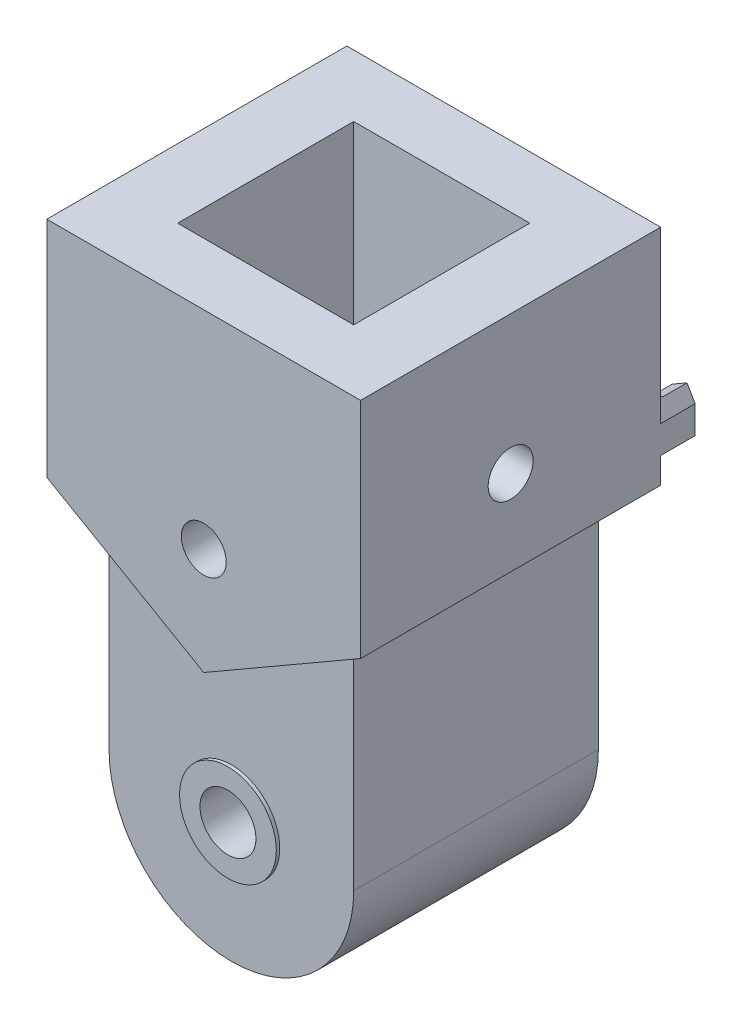
SolidWorks part; units mm, degrees
material "PETG"
ref_plane "Front Plane" through (0, 0, 0) normal (0, 0, 1) x (1, 0, 0)
ref_plane "Top Plane" through (0, 0, 0) normal (0, 1, 0) x (1, 0, 0)
ref_plane "Right Plane" through (0, 0, 0) normal (1, 0, 0) x (0, 0, -1)
sketch "Sketch1" plane through (0, 0, 0) normal (0, 1, 0) x (1, 0, 0)
  line L1 (-12.7375, -12.7375) -> (12.7375, -12.7375)
  line L2 (-12.7375, -12.7375) -> (-12.7375, 12.7375)
  line L3 (-12.7375, 12.7375) -> (12.7375, 12.7375)
  line L4 (12.7375, -12.7375) -> (12.7375, 12.7375)
  line L5 (-17.7, -17.7) -> (17.7, -17.7)
  line L6 (-17.7, -17.7) -> (-17.7, 17.7)
  line L7 (-17.7, 17.7) -> (17.7, 17.7)
  line L8 (17.7, -17.7) -> (17.7, 17.7)
  point P8 (0, -17.7)
  point P9 (0, -12.7375)
  point P12 (-17.7, 0)
  point P13 (-12.7375, 0)
  dimension "D1" = 25.475
  dimension "D2" = 35.4
extrude "Boss-Extrude1" add sketch "Sketch1" along normal blind 50.0375
extrude "Boss-Extrude2" add sketch "Sketch1<3>" against normal blind 9.9625 contours L1 L4 L3 L2 | L5 L8 L7 L6 L4 L1 L2 L3 region at (0, 0, 0) region at (-17.1994, 0, 0)
sketch "Sketch1<3>" plane through (0, 0, 0) normal (0, 1, 0) x (1, 0, 0) same geometry as "Sketch1"
sketch "Sketch2" plane through (0, 0, -17.7) normal (0, 0, 1) x (1, 0, 0)
  line L1 (17.7, 50.0375) -> (17.7, -9.9625) construction
  line L4 (-17.7, -9.9625) -> (17.7, -9.9625) construction
  line L5 (-17.7, -15.9125) -> (-17.7, -9.9625)
  line L6 (17.7, -9.9625) -> (17.7, -15.9125)
  line L7 (17.7, -9.9625) -> (-17.7, -9.9625)
  circle A0 centre (0, -15.9625) radius 4.05
  circle A2 centre (0, -15.9625) radius 11 construction
  arc A3 (17.7, -15.9125) -> (-17.7, -15.9125) centre (0, -15.9125) cw
  dimension "D1" = 8.1
  dimension "D3" = 22
  dimension "D2" = 6
  dimension "D4" = 5.95
extrude "Boss-Extrude5" add sketch "Sketch2" along normal up to surface (35.4 mm away) up to face at (0, 20.0375, 17.7)
ref_plane "Plane1" through (0, -33.6125, 0) normal (0, -1, 0) x (-1, 0, 0)
sketch "Sketch3" plane through (0, -33.6125, 0) normal (0, -1, 0) x (-1, 0, 0)
  circle A0 centre (0, 0) radius 3.15
  dimension "D1" = 6.3
extrude "Cut-Extrude1" cut sketch "Sketch3" against normal through all
sketch "Sketch4" plane through (0, -33.6125, 0) normal (0, -1, 0) x (-1, 0, 0)
  circle A0 centre (0, 0) radius 5.5
  dimension "D1" = 11
extrude "Cut-Extrude2" cut sketch "Sketch4" against normal offset from surface (25.6125 mm away) 8 up to face at (0, 0, 3.15)
sketch "Sketch5" plane through (0, 0, 17.7) normal (0, 0, 1) x (1, 0, 0)
  circle A0 centre (0, -15.9625) radius 7
  circle A1 centre (0, -15.9625) radius 4.05 construction
  circle M6 centre (0, -15.9625) radius 4.05
  dimension "D1" = 14
extrude "Boss-Extrude6" add sketch "Sketch5" along normal blind 0.5 contours A0 M6 region at (-6.802, -15.9625, 17.7)
mirror "Mirror1" about plane through (0, 0, 0) normal (0, 0, 1) of "Boss-Extrude6"
sketch "Sketch6" plane through (0, 0, 17.7) normal (0, 0, 1) x (1, 0, 0)
  line L5 (8.875, -31.2845) -> (52.1763, -6.2845) construction
  line L6 (-8.875, -0.5405) -> (34.4263, 24.4595) construction
  line L7 (52.1763, -6.2845) -> (34.4263, 24.4595) construction
  line L8 (0, -16) -> (0, -79.4793) construction
  line L9 (17.7, 50.0375) -> (17.7, -15.9125) construction
  line L10 (17.7, 14.8025) -> (-17.7, 14.8025)
  line L11 (17.7, 14.8025) -> (17.7, 50.0375)
  line L12 (17.7, 50.0375) -> (-17.7, 50.0375)
  line L13 (-17.7, 14.8025) -> (-17.7, 50.0375)
  line L14 (17.7, 14.8025) -> (0, 4.5834)
  line L15 (0, 4.5834) -> (-17.7, 14.8025)
  circle A1 centre (0, -15.9125) radius 17.75
  arc A2 (-17.7, -15.9125) -> (17.7, -15.9125) centre (0, -15.9125) ccw construction
  line M4 (-17.7, 50.0375) -> (-17.7, -15.9125)
  line M6 (17.7, -15.9125) -> (17.7, 50.0375)
  line M7 (17.7, 50.0375) -> (-17.7, 50.0375)
  dimension "D1" = 50
  dimension "D2" = 120
  dimension "D3" = 35.5
extrude "Boss-Extrude7" add sketch "Sketch6" along normal blind 4 contours L14 L10 M4 | L10 M6 M7 M4 region at (0, 11.3962, 17.7) region at (0, 32.42, 17.7)
sketch "Sketch7" plane through (0, 0, 21.7) normal (0, 0, 1) x (1, 0, 0)
  line L0 (17.7, 50.0375) -> (-17.7, 50.0375) construction
  line L1 (17.7, 20.0375) -> (0, 20.0375) construction
  line L2 (17.7, 14.8025) -> (17.7, 50.0375) construction
  line L3 (0, 20.0375) -> (-17.7, 20.0375) construction
  line L4 (-17.7, 50.0375) -> (-17.7, 14.8025) construction
  circle A0 centre (0, 20.0375) radius 3.25
  dimension "D1" = 30
  dimension "D2" = 6.5
extrude "Cut-Extrude3" cut sketch "Sketch7" against normal up to next
mirror "Mirror2" about plane through (0, 0, 0) normal (0, 0, 1) of "Boss-Extrude7", "Cut-Extrude3"
sketch "Sketch9" plane through (0, 0, 0) normal (0, 0, 1) x (1, 0, 0)
  line L0 (-17.7, 14.8025) -> (-22.7, 17.6893)
  line L1 (0, 4.5834) -> (-17.7, 14.8025) construction
  line L3 (-17.7, 14.8025) -> (-17.7, 50.0375)
  line L4 (-17.7, 50.0375) -> (-22.7, 50.0375)
  line L5 (-22.7, 17.6893) -> (-22.7, 50.0375)
  line L6 (0, 0) -> (0, 50000) construction
  line L7 (22.7, 17.6893) -> (22.7, 50.0375)
  line L8 (17.7, 50.0375) -> (22.7, 50.0375)
  line L9 (17.7, 14.8025) -> (17.7, 50.0375)
  line L10 (17.7, 14.8025) -> (22.7, 17.6893)
  dimension "D1" = 5
extrude "Boss-Extrude9" add sketch "Sketch9" along normal up to surface and the other way up to surface up to face at (3.25, 20.0375, 21.7) other way up to face at (3.25, 20.0375, -21.7)
sketch "Sketch10" plane through (0, 0, 0) normal (-1, 0, 0) x (0, 0, 1)
  line L0 (21.7, 50.0375) -> (-21.7, 50.0375) construction
  circle A0 centre (0, 30.0375) radius 3.25
  dimension "D1" = 6.5
  dimension "D2" = 20
extrude "Cut-Extrude4" cut sketch "Sketch10" against normal through all both and the other way through all
sketch "Sketch11" plane through (0, 0, -21.7) normal (0, 0, -1) x (-1, 0, 0)
  line L0 (-12.9904, 12.0834) -> (-24.3137, 18.6209)
  line L1 (-12.9904, 12.0834) -> (-9.4716, 18.1781)
  line L2 (-24.3137, 18.6209) -> (-20.7949, 24.7156)
  line L3 (-9.4716, 18.1781) -> (-20.7949, 24.7156)
  line L4 (-22.7, 17.6893) -> (0, 4.5834) construction
  line L5 (-12.9904, 12.0834) -> (-11.2583, 11.0834)
  line L6 (-11.2583, 11.0834) -> (-6.7396, 18.9101)
  line L7 (-6.7396, 18.9101) -> (-8.9046, 20.1601)
  line L8 (-8.9046, 20.1601) -> (-9.9046, 18.4281)
  line L9 (-12.9904, 12.0834) -> (-11.2583, 11.0834)
  line L10 (-20.3619, 24.4656) -> (-19.3619, 26.1976)
  line L11 (-19.3619, 26.1976) -> (-21.527, 27.4476)
  line L12 (-21.527, 27.4476) -> (-22.7, 25.4159)
  line L13 (-22.7, 17.6893) -> (-22.7, 50.0375) construction
  line L14 (-22.7, 25.4159) -> (-22.7, 21.4159)
  line L15 (-18.5974, 23.4468) -> (-16.8653, 22.4468)
  line L16 (-18.5974, 23.4468) -> (-17.5974, 25.1789)
  line L17 (-16.8653, 22.4468) -> (-15.8653, 24.1789)
  line L18 (-17.5974, 25.1789) -> (-15.8653, 24.1789)
  line L19 (-13.4012, 20.4468) -> (-11.6692, 19.4468)
  line L20 (-13.4012, 20.4468) -> (-12.4012, 22.1789)
  line L21 (-11.6692, 19.4468) -> (-10.6692, 21.1789)
  line L22 (-12.4012, 22.1789) -> (-10.6692, 21.1789)
  line L23 (-11.1692, 20.3129) -> (-9.4046, 19.2941) construction
  line L24 (-19.8619, 25.3316) -> (-18.0974, 24.3129) construction
  line L25 (-19.3619, 26.1976) -> (-8.9046, 20.1601)
  point P4 (0, 4.5834)
  point P19 (-16.7313, 24.6789)
  point P30 (-11.5352, 21.6789)
  line M19 (-22.7, 50.0375) -> (-22.7, 17.6893)
  line M20 (-22.7, 17.6893) -> (0, 4.5834)
  dimension "D1" = 13.075
  dimension "D2" = 7.0375
  dimension "D3" = 15
  dimension "D4" = 2
  dimension "D5" = 0.5
  dimension "D6" = 0.5
  dimension "D7" = 2
  dimension "D8" = 2
  dimension "D9" = 6
extrude "Boss-Extrude10" add sketch "Sketch11" along normal blind 5 contours L11 L12 L2 L3 L10 M19 | L7 L8 L3 L1 L6 M20 region at (9.8295, 15.6893, -21.7) region at (21.4509, 25.0541, -21.7)
extrude "Boss-Extrude11" add sketch "Sketch11<3>" along normal blind 1.5 contours L25 L17 L3 L20 | L18 L16 L3 L17 | L25 L10 L3 L16 | L22 L20 L3 L21 | L25 L21 L3 L8 region at (10.2869, 19.8035, -21.7) region at (12.0352, 20.8129, -21.7) region at (18.9796, 24.8222, -21.7) region at (14.6333, 22.3129, -21.7) region at (17.2313, 23.8129, -21.7)
sketch "Sketch11<3>" plane through (0, 0, -21.7) normal (0, 0, -1) x (-1, 0, 0) same geometry as "Sketch11"
chamfer "Chamfer1" distance 1.5 angle 45 1 edges at (14.1333, 23.1789, -21.7)
mirror "Mirror3" about plane through (0, 0, 0) normal (1, 0, 0) of "Boss-Extrude11", "Chamfer1", "Boss-Extrude10"
equation "\"tol_dia_id_intfc\"= 0.0500mm ' For hole diameters - Interference fit"
equation "\"tol_dia_id_slip\"= 0.0750mm ' For hole diameters - Slip fit"
equation "\"tol_dia_id_clear\"= 0.1000mm ' For hole diameters - Clearance fit"
equation "\"tol_dia_od_intfc\"= 0.0500mm ' For shaft diameters - Interference fit"
equation "\"tol_dia_od_slip\"= 0.0750mm ' For shaft diameters - Slip fit"
equation "\"tol_dia_od_clear\"= 0.1000mm ' For shaft diameters - Clearance fit"
equation "\"tol_general_intfc\"= 0.0250mm ' For general parts (Horiz) - Interference fit"
equation "\"tol_general_slip\"= 0.0375mm ' For general parts (Horiz) - Slip fit"
equation "\"tol_general_clear\"= 0.0500mm ' For general parts (Horiz) - Clearance fit"
equation "\"tol_layer_intfc\"= 0.0250mm ' For all parts (Vert) - Interference fit"
equation "\"tol_layer_slip\"= 0.0375mm ' For all parts (Vert) - Slip fit"
equation "\"tol_layer_clear\"= 0.0500mm ' For all parts (Vert) - Clearance fit"
equation "\"tol_corner_rad\"= 0.100mm ' For corners that fit into other parts"
equation "\"D1@Sketch1\"=25.40mm+\"tol_general_slip\"*2"
equation "\"D2@Sketch1\"=25.4+10"
equation "\"D1@Boss-Extrude1\"= 50.00mm + \"tol_layer_slip\""
equation "\"D1@Boss-Extrude2\"=10.00mm-\"tol_layer_slip\""
equation "\"D1@Sketch2\"=8.00mm+\"tol_dia_id_clear\""
equation "\"D4@Sketch2\"=6.00mm-\"tol_dia_od_clear\"/2"
equation "\"D3@Sketch6\"=25.4+10+\"tol_general_clear\"*2"
equation "\"D1@Sketch11\"=13mm+\"tol_general_slip\"*2"
equation "\"D2@Sketch11\"=7mm+\"tol_general_slip\""
equation "\"D6@Sketch11\"=\"D5@Sketch11\""
equation "\"D8@Sketch11\"=\"D7@Sketch11\""
